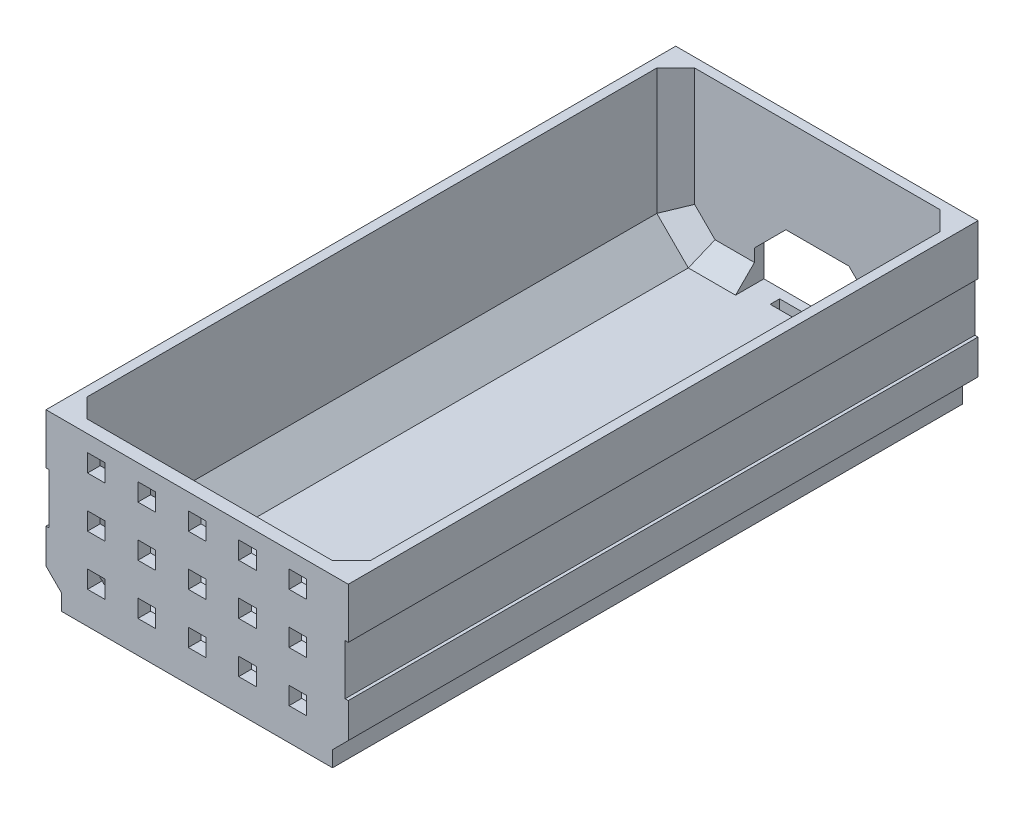
SolidWorks part; units mm, degrees
ref_plane "Plano frontal" through (0, 0, 0) normal (0, 0, 1) x (1, 0, 0)
ref_plane "Plano superior" through (0, 0, 0) normal (0, 1, 0) x (1, 0, 0)
ref_plane "Plano direito" through (0, 0, 0) normal (1, 0, 0) x (0, 0, -1)
sketch "Esboço1" plane through (0, 0, 0) normal (0, 0, 1) x (1, 0, 0)
  line L0 (-24, 14) -> (-24, -14) construction
  line L1 (24, 14) -> (24, -14) construction
  line L2 (-22.5, 12.5) -> (-22.5, -7.5)
  line L3 (-17.5, -12.5) -> (17.5, -12.5)
  line L4 (22.5, 12.5) -> (22.5, -7.5)
  line L5 (-22.5, 12.5) -> (22.5, -12.5) construction
  line L6 (-22.5, -12.5) -> (22.5, 12.5) construction
  line L7 (24, 12.5) -> (24, -9)
  line L8 (-19, -14) -> (19, -14)
  line L9 (-24, 12.5) -> (-24, -9)
  line L10 (-22.5, 12.5) -> (-24, 12.5)
  line L11 (22.5, 12.5) -> (24, 12.5)
  line L12 (-22.5, -12.5) -> (22.5, -12.5) construction
  line L13 (-22.5, 12.5) -> (22.5, 12.5) construction
  line L14 (-24, 14) -> (24, 14) construction
  line L15 (22.5, 12.5) -> (22.5, -12.5) construction
  line L16 (17.5, -12.5) -> (22.5, -7.5)
  line L17 (-24, -14) -> (24, -14) construction
  line L18 (24, -9) -> (19, -14)
  line L19 (-22.5, 12.5) -> (-22.5, -12.5) construction
  line L20 (-22.5, -7.5) -> (-17.5, -12.5)
  line L21 (-24, -9) -> (-19, -14)
  point P0 (0, 0)
  dimension "D1" = 25
  dimension "D2" = 45
  dimension "D3" = 1.5
extrude "Ressalto-extrusão1" add sketch "Esboço1" along normal blind 100
sketch "Esboço3" plane through (0, -12.5, 0) normal (0, 1, 0) x (1, 0, 0)
  line L0 (22.5, -100) -> (22.5, 0) construction
  line L1 (-22.5, 0) -> (22.5, 0)
  line L2 (-22.5, 0) -> (-22.5, -1.5)
  line L3 (-22.5, -1.5) -> (22.5, -1.5)
  line L4 (22.5, 0) -> (22.5, -1.5)
  dimension "D1" = 1.5
extrude "Ressalto-extrusão3" add sketch "Esboço3" along normal up to surface (25 mm away) up to face at (-23.25, 12.5, 50)
sketch "Esboço4" plane through (0, 0, 1.5) normal (0, 0, 1) x (1, 0, 0)
  line L0 (17.5, -12.5) -> (-17.5, -12.5) construction
  line L1 (-10, -12.5) -> (10, -12.5)
  line L2 (-10, -12.5) -> (-10, -7.5)
  line L3 (-5, -2.5) -> (5, -2.5)
  line L4 (10, -12.5) -> (10, -7.5)
  line L5 (-10, -7.5) -> (-5, -2.5)
  line L6 (5, -2.5) -> (10, -7.5)
  point P1 (10, -2.5)
  point P2 (-10, -2.5)
  point P4 (0, -12.5)
  point P5 (0, -12.5)
extrude "Corte-extrusão1" cut sketch "Esboço4" against normal through all
sketch "Esboço5" plane through (0, -12.5, 0) normal (0, 1, 0) x (1, 0, 0)
  line L0 (0, 0) -> (0, -2.25) construction
  line L1 (22.5, -1.5) -> (-22.5, -1.5) construction
  line L2 (-6, -3) -> (6, -3)
  line L3 (-6, -3) -> (-6, -1.5)
  line L4 (-6, -1.5) -> (6, -1.5)
  line L5 (6, -3) -> (6, -1.5)
  line L6 (-6, -3) -> (6, -1.5) construction
  line L7 (-6, -1.5) -> (6, -3) construction
  dimension "D1" = 2.25
  dimension "D2" = 12
extrude "Corte-extrusão2" cut sketch "Esboço5" against normal through all
sketch "Esboço6" plane through (0, -12.5, 0) normal (0, 1, 0) x (1, 0, 0)
  line L0 (22.5, -100) -> (22.5, -1.5) construction
  line L1 (-22.5, -100) -> (22.5, -100)
  line L2 (-22.5, -100) -> (-22.5, -98)
  line L3 (-22.5, -98) -> (22.5, -98)
  line L4 (22.5, -100) -> (22.5, -98)
extrude "Ressalto-extrusão4" add sketch "Esboço6" along normal up to surface (25 mm away) up to face at (0, 12.5, 50.375)
sketch "Esboço7" plane through (0, 0, 100) normal (0, 0, 1) x (1, 0, 0)
  line L0 (0, 12.5) -> (0, 8.5) construction
  line L1 (24, 12.5) -> (-24, 12.5) construction
  line L2 (0, 8.5) -> (1, 8.5) construction
  line L3 (1, 8.5) -> (0, 8.5) construction
  line L4 (0, 8.5) -> (0, 0.5) construction
  line L5 (0, 0.5) -> (1, 0.5) construction
  line L6 (1, 0.5) -> (0, 0.5) construction
  line L7 (0, 0.5) -> (0, -7.5) construction
  line L8 (0, 8.5) -> (-8, 8.5) construction
  line L9 (-8, 8.5) -> (-16, 8.5) construction
  line L10 (-9.4, 9.9) -> (-6.6, 9.9)
  line L11 (-17.4, 9.9) -> (-14.6, 9.9)
  line L12 (-17.4, 9.9) -> (-17.4, 7.1)
  line L13 (-17.4, 7.1) -> (-14.6, 7.1)
  line L14 (-14.6, 9.9) -> (-14.6, 7.1)
  line L15 (-17.4, 9.9) -> (-14.6, 7.1) construction
  line L16 (-17.4, 7.1) -> (-14.6, 9.9) construction
  line L17 (-9.4, 9.9) -> (-9.4, 7.1)
  line L18 (-9.4, 7.1) -> (-6.6, 7.1)
  line L19 (-6.6, 9.9) -> (-6.6, 7.1)
  line L20 (-9.4, 9.9) -> (-6.6, 7.1) construction
  line L21 (-9.4, 7.1) -> (-6.6, 9.9) construction
  line L22 (-1.4, 9.9) -> (1.4, 9.9)
  line L23 (-1.4, 9.9) -> (-1.4, 7.1)
  line L24 (-1.4, 7.1) -> (1.4, 7.1)
  line L25 (1.4, 9.9) -> (1.4, 7.1)
  line L26 (-1.4, 9.9) -> (1.4, 7.1) construction
  line L27 (-1.4, 7.1) -> (1.4, 9.9) construction
  line L28 (6.6, 9.9) -> (9.4, 9.9)
  line L29 (6.6, 9.9) -> (6.6, 7.1)
  line L30 (6.6, 7.1) -> (9.4, 7.1)
  line L31 (9.4, 9.9) -> (9.4, 7.1)
  line L32 (6.6, 9.9) -> (9.4, 7.1) construction
  line L33 (6.6, 7.1) -> (9.4, 9.9) construction
  line L34 (14.6, 9.9) -> (17.4, 9.9)
  line L35 (14.6, 9.9) -> (14.6, 7.1)
  line L36 (14.6, 7.1) -> (17.4, 7.1)
  line L37 (17.4, 9.9) -> (17.4, 7.1)
  line L38 (14.6, 9.9) -> (17.4, 7.1) construction
  line L39 (14.6, 7.1) -> (17.4, 9.9) construction
  line L40 (-9.4, 1.9) -> (-6.6, 1.9)
  line L41 (-9.4, 1.9) -> (-9.4, -0.9)
  line L42 (-9.4, -0.9) -> (-6.6, -0.9)
  line L43 (-6.6, 1.9) -> (-6.6, -0.9)
  line L44 (-9.4, 1.9) -> (-6.6, -0.9) construction
  line L45 (-9.4, -0.9) -> (-6.6, 1.9) construction
  line L46 (-1.4, 1.9) -> (1.4, 1.9)
  line L47 (-1.4, 1.9) -> (-1.4, -0.9)
  line L48 (-1.4, -0.9) -> (1.4, -0.9)
  line L49 (1.4, 1.9) -> (1.4, -0.9)
  line L50 (-1.4, 1.9) -> (1.4, -0.9) construction
  line L51 (-1.4, -0.9) -> (1.4, 1.9) construction
  line L52 (6.6, 1.9) -> (9.4, 1.9)
  line L53 (6.6, 1.9) -> (6.6, -0.9)
  line L54 (6.6, -0.9) -> (9.4, -0.9)
  line L55 (9.4, 1.9) -> (9.4, -0.9)
  line L56 (6.6, 1.9) -> (9.4, -0.9) construction
  line L57 (6.6, -0.9) -> (9.4, 1.9) construction
  line L58 (14.6, 1.9) -> (17.4, 1.9)
  line L59 (14.6, 1.9) -> (14.6, -0.9)
  line L60 (14.6, -0.9) -> (17.4, -0.9)
  line L61 (17.4, 1.9) -> (17.4, -0.9)
  line L62 (14.6, 1.9) -> (17.4, -0.9) construction
  line L63 (14.6, -0.9) -> (17.4, 1.9) construction
  line L64 (-9.4, -6.1) -> (-6.6, -6.1)
  line L65 (-9.4, -6.1) -> (-9.4, -8.9)
  line L66 (-9.4, -8.9) -> (-6.6, -8.9)
  line L67 (-6.6, -6.1) -> (-6.6, -8.9)
  line L68 (-9.4, -6.1) -> (-6.6, -8.9) construction
  line L69 (-9.4, -8.9) -> (-6.6, -6.1) construction
  line L70 (-1.4, -6.1) -> (1.4, -6.1)
  line L71 (-1.4, -6.1) -> (-1.4, -8.9)
  line L72 (-1.4, -8.9) -> (1.4, -8.9)
  line L73 (1.4, -6.1) -> (1.4, -8.9)
  line L74 (-1.4, -6.1) -> (1.4, -8.9) construction
  line L75 (-1.4, -8.9) -> (1.4, -6.1) construction
  line L76 (6.6, -6.1) -> (9.4, -6.1)
  line L77 (6.6, -6.1) -> (6.6, -8.9)
  line L78 (6.6, -8.9) -> (9.4, -8.9)
  line L79 (9.4, -6.1) -> (9.4, -8.9)
  line L80 (6.6, -6.1) -> (9.4, -8.9) construction
  line L81 (6.6, -8.9) -> (9.4, -6.1) construction
  line L82 (14.6, -6.1) -> (17.4, -6.1)
  line L83 (14.6, -6.1) -> (14.6, -8.9)
  line L84 (14.6, -8.9) -> (17.4, -8.9)
  line L85 (17.4, -6.1) -> (17.4, -8.9)
  line L86 (14.6, -6.1) -> (17.4, -8.9) construction
  line L87 (14.6, -8.9) -> (17.4, -6.1) construction
  line L88 (-17.4, 1.9) -> (-14.6, 1.9)
  line L89 (-17.4, 1.9) -> (-17.4, -0.9)
  line L90 (-17.4, -0.9) -> (-14.6, -0.9)
  line L91 (-14.6, 1.9) -> (-14.6, -0.9)
  line L92 (-17.4, 1.9) -> (-14.6, -0.9) construction
  line L93 (-17.4, -0.9) -> (-14.6, 1.9) construction
  line L94 (-17.4, -6.1) -> (-14.6, -6.1)
  line L95 (-17.4, -6.1) -> (-17.4, -8.9)
  line L96 (-17.4, -8.9) -> (-14.6, -8.9)
  line L97 (-14.6, -6.1) -> (-14.6, -8.9)
  line L98 (-17.4, -6.1) -> (-14.6, -8.9) construction
  line L99 (-17.4, -8.9) -> (-14.6, -6.1) construction
  dimension "D1" = 2.8
  dimension "D2" = 5
  dimension "D3" = 3
extrude "Corte-extrusão3" cut sketch "Esboço7" against normal blind 10
sketch "Esboço8" plane through (0, 0, 0) normal (0, 0, -1) x (-1, 0, 0)
  line L3 (-22.5, -10.5) -> (-22.5, -12.5)
  line L4 (-20.5, -12.5) -> (-22.5, -10.5)
  line L5 (-22.5, -12.5) -> (-20.5, -12.5)
  line L6 (-22.5, -10.5) -> (-22.5, -12.5)
  line L7 (-20.5, -12.5) -> (-22.5, -10.5)
  line L8 (-22.5, -12.5) -> (-20.5, -12.5)
  line L9 (20.5, -12.5) -> (22.5, -12.5)
  line L10 (22.5, -10.5) -> (20.5, -12.5)
  line L11 (22.5, -12.5) -> (22.5, -10.5)
  line L12 (20.5, -12.5) -> (22.5, -12.5)
  line L13 (22.5, -10.5) -> (20.5, -12.5)
  line L14 (22.5, -12.5) -> (22.5, -10.5)
  dimension "D1" = 0
  dimension "D2" = 0
extrude "Corte-extrusão4" cut sketch "Esboço8" against normal through all
sketch "Esboço9" plane through (0, 0, 0) normal (0, 0, -1) x (-1, 0, 0)
  line L0 (-19, -14) -> (-21.5, -14)
  line L1 (-21.5, -14) -> (-21.5, -11.5)
  line L2 (-19, -14) -> (-24, -9) construction
  line L3 (-21.5, -11.5) -> (-19, -14)
  line L4 (19, -14) -> (21.5, -14)
  line L5 (21.5, -14) -> (21.5, -11.5)
  line L6 (24, -9) -> (19, -14) construction
  line L7 (21.5, -11.5) -> (19, -14)
extrude "Ressalto-extrusão5" add sketch "Esboço9" against normal through all
sketch "Esboço10" plane through (0, 0, 0) normal (0, 0, -1) x (-1, 0, 0)
  line L0 (0, 0) -> (0, 16.2548) construction
  line L1 (-24, 12.5) -> (-24, 4.5) construction
  line L2 (-24, -9) -> (-24, 12.5) construction
  line L3 (-24, 4.5) -> (-23.5, 4.5)
  line L4 (-23.5, 4.5) -> (-23.5, -3.5)
  line L5 (-23.5, -3.5) -> (-24, -3.5)
  line L6 (-24, -3.5) -> (-24, 4.5)
  line L7 (24, -3.5) -> (24, 4.5)
  line L8 (23.5, -3.5) -> (24, -3.5)
  line L9 (23.5, 4.5) -> (23.5, -3.5)
  line L10 (24, 4.5) -> (23.5, 4.5)
extrude "Corte-extrusão5" cut sketch "Esboço10" against normal through all
chamfer "Chanfro1" distance 3 angle 45 5 edges at (-22.5, 2.5, 98) (-20, -10, 98) (22.5, 2.5, 98) (20, -10, 98) (0, -12.5, 98)
chamfer "Chanfro2" distance 3 angle 45 6 edges at (-22.5, 2.5, 1.5) (-20, -10, 1.5) (-13.75, -12.5, 1.5) (13.75, -12.5, 1.5) (20, -10, 1.5) (22.5, 2.5, 1.5)
